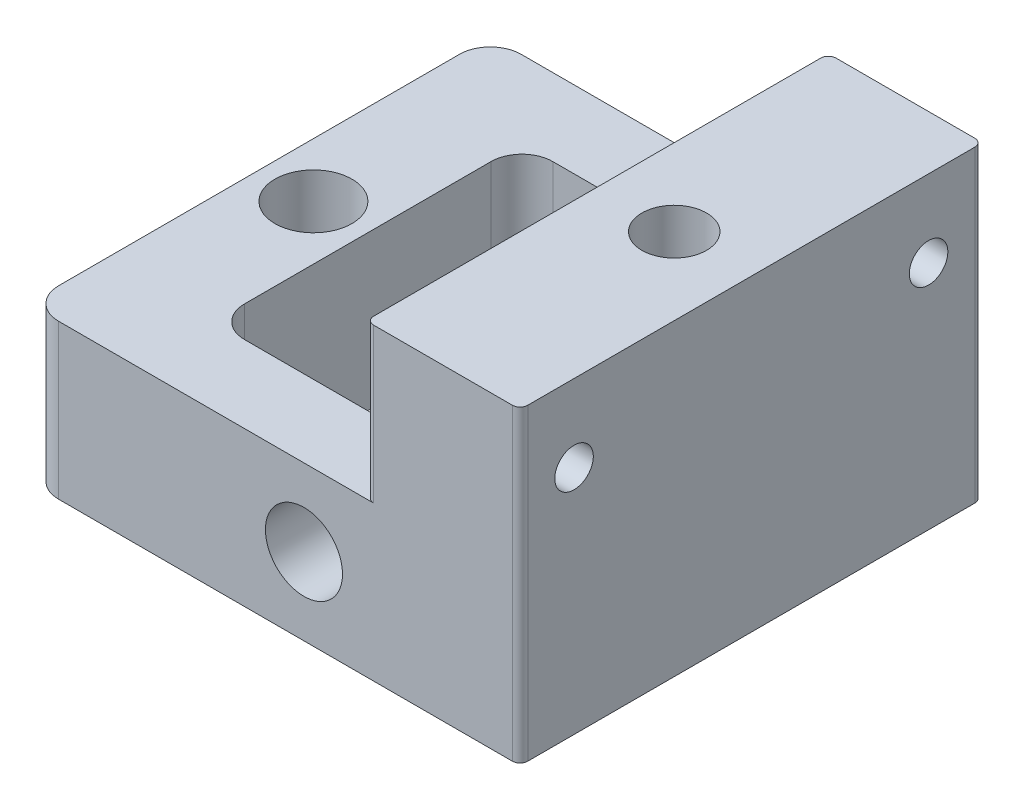
SolidWorks part; units mm, degrees
material "AISI 1045 Steel, cold drawn"
ref_plane "Front Plane" through (0, 0, 0) normal (0, 0, 1) x (1, 0, 0)
ref_plane "Top Plane" through (0, 0, 0) normal (0, 1, 0) x (1, 0, 0)
ref_plane "Right Plane" through (0, 0, 0) normal (1, 0, 0) x (0, 0, -1)
sketch "Sketch1" plane through (0, 0, 0) normal (0, 1, 0) x (1, 0, 0)
  line L1 (7.44, -10) -> (-7.44, -10)
  line L2 (7.44, -10) -> (7.44, 10)
  line L3 (7.44, 10) -> (-7.44, 10)
  line L4 (-7.44, -10) -> (-7.44, 10)
  line L5 (7.44, -10) -> (-7.44, 10) construction
  line L6 (7.44, 10) -> (-7.44, -10) construction
  line L7 (17.44, -15) -> (-14.49, -15)
  line L8 (17.44, -15) -> (17.44, 15)
  line L9 (17.44, 15) -> (-14.49, 15)
  line L10 (-14.49, -15) -> (-14.49, 15)
  line L11 (17.44, -15) -> (-14.49, 15) construction
  line L12 (17.44, 15) -> (-14.49, -15) construction
  point P0 (0, 0)
  point P6 (1.475, 0)
  point P11 (0, 0)
  dimension "D1" = 14.88
  dimension "D2" = 20
  dimension "D3" = 7.05
  dimension "D4" = 5
  dimension "D5" = 10
extrude "Boss-Extrude1" add sketch "Sketch1" along normal blind 10
sketch "Sketch2" plane through (0, 10, 0) normal (0, 1, 0) x (1, 0, 0)
  line L0 (-14.49, -15) -> (17.44, -15) construction
  line L1 (17.44, 15) -> (7.44, 15)
  line L2 (17.44, 15) -> (17.44, -15)
  line L3 (17.44, -15) -> (7.44, -15)
  line L4 (7.44, 15) -> (7.44, -15)
  line L5 (7.44, -10) -> (7.44, 10) construction
extrude "Boss-Extrude2" add sketch "Sketch2" along normal blind 10
hole_wizard "Tap Drill for M5x0.8 Tap1" positions "Sketch3" profile "Sketch4" hole size "M5x0.8" standard "ANSI Metric" end condition through all
sketch "Sketch3" plane through (0, 20, 0) normal (0, 1, 0) x (1, 0, 0)
  line L1 (17.44, 15) -> (7.44, -15) construction
  point P0 (12.44, 0)
  point P11 (13.44, 0)
sketch "Sketch4" plane through (12.44, 20, 0) normal (1, 0, 0) x (0, 0, 1)
  line L0 (0, 0) -> (0, 20)
  line L1 (0, 20) -> (2.1, 20)
  line L2 (2.1, 20) -> (2.1, 0)
  line L5 (2.1, 0) -> (0, 0)
  line L11 (0, -6.35) -> (0, 107.95) construction
  dimension "Thru Hole Dia." = 4.2
  dimension "Thru Hole Depth" = 20
fillet "Fillet2" radius 2 4 edges at (-7.44, 5, 10) (-7.44, 5, -10) (7.44, 5, -10) (7.44, 5, 10)
sketch "Sketch5" plane through (0, 0, -10) normal (0, 0, 1) x (1, 0, 0)
  line L0 (7.44, 10) -> (7.44, 0) construction
  line L1 (5.44, 10) -> (-5.44, 10) construction
  circle A0 centre (3.42, 5) radius 2.5
  dimension "D2" = 5
  dimension "D1" = 4.02
  dimension "D3" = 5
extrude "Cut-Extrude2" cut sketch "Sketch5" along normal through all
hole_wizard "Tap Drill for M4x0.7 Tap1" positions "Sketch6" profile "Sketch7" hole size "M4x0.7" standard "ANSI Metric" end condition through all
sketch "Sketch6" plane through (0, 0, -10) normal (0, 0, 1) x (1, 0, 0)
  point P0 (3.42, 5)
sketch "Sketch7" plane through (3.42, 5, -10) normal (1, 0, 0) x (0, -1, 0)
  line L0 (0, 0) -> (0, 5)
  line L1 (0, 5) -> (1.65, 5)
  line L2 (1.65, 5) -> (1.65, 0)
  line L5 (1.65, 0) -> (0, 0)
  line L11 (0, -6.35) -> (0, 107.95) construction
  dimension "Thru Hole Dia." = 3.3
  dimension "Thru Hole Depth" = 5
fillet "Fillet3" radius 2 2 edges at (-14.49, 5, -15) (-14.49, 5, 15)
fillet "Fillet4" radius 0.5 4 edges at (17.44, 10, 15) (17.44, 10, -15) (7.44, 15, -15) (7.44, 15, 15)
hole_wizard "Tap Drill for M3x0.5 Tap1" positions "Sketch8" profile "Sketch9" hole size "M3x0.5" standard "ANSI Metric" end condition through all
sketch "Sketch8" plane through (7.44, 0, 0) normal (-1, 0, 0) x (0, 0, 1)
  line L0 (-11.5, 15) -> (11.5, 15) construction
  line L2 (-14.5, 20) -> (14.5, 20) construction
  line L3 (-14.5, 20) -> (-14.5, 10) construction
  point P1 (-11.5, 15)
  point P2 (11.5, 15)
  point P7 (0, 20)
  point P8 (0, 15)
  point P11 (-14.5, 15)
  dimension "D1" = 23
sketch "Sketch9" plane through (7.44, 15, -11.5) normal (0, 1, 0) x (0, 0, 1)
  line L0 (0, 0) -> (0, 10)
  line L1 (0, 10) -> (1.25, 10)
  line L2 (1.25, 10) -> (1.25, 0)
  line L5 (1.25, 0) -> (0, 0)
  line L11 (0, -6.35) -> (0, 107.95) construction
  dimension "Thru Hole Dia." = 2.5
  dimension "Thru Hole Depth" = 10
hole_wizard "Ø5.0 (5) Diameter Hole1" positions "Sketch10" profile "Sketch11" hole size "Ø5.0" standard "ANSI Metric" end condition through all
sketch "Sketch10" plane through (0, 10, 0) normal (0, 1, 0) x (1, 0, 0)
  line L0 (-14.49, 0) -> (-7.44, 0) construction
  line L1 (-14.49, 13) -> (-14.49, -13) construction
  line L2 (-7.44, 8) -> (-7.44, -8) construction
  point P0 (-10.965, 0)
  point P13 (0, 0)
  point P14 (-10.965, 0)
sketch "Sketch11" plane through (-10.965, 10, 0) normal (1, 0, 0) x (0, 0, 1)
  line L0 (0, 0) -> (0, 10)
  line L1 (0, 10) -> (2.5, 10)
  line L2 (2.5, 10) -> (2.5, 0)
  line L5 (2.5, 0) -> (0, 0)
  line L11 (0, -6.35) -> (0, 107.95) construction
  dimension "Thru Hole Dia." = 5
  dimension "Thru Hole Depth" = 10
